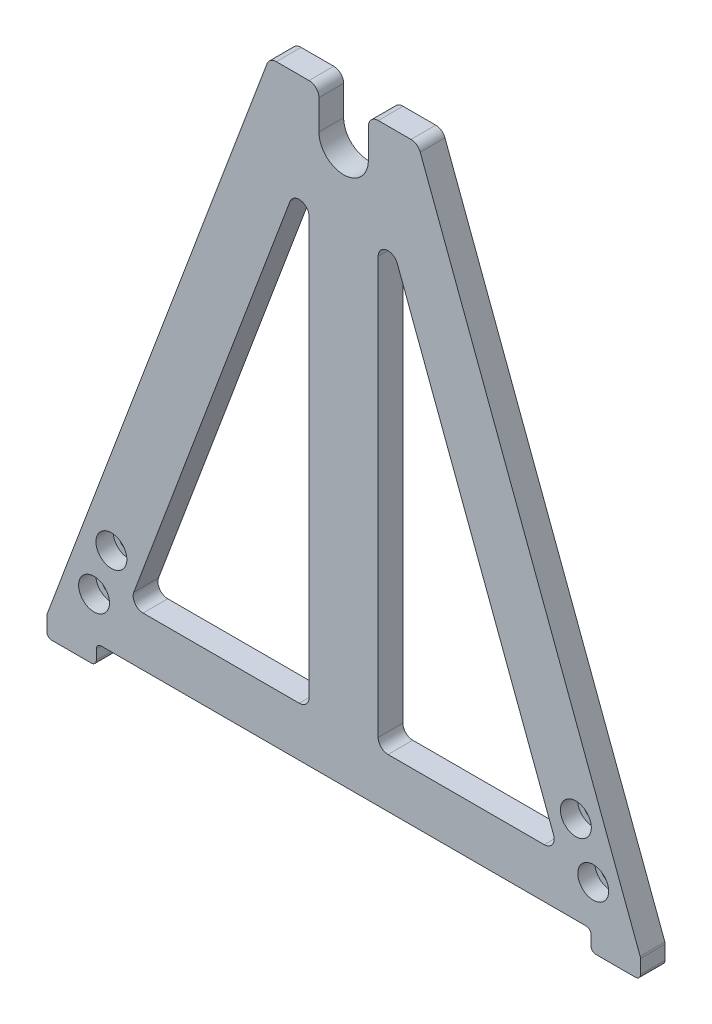
SolidWorks part; units mm, degrees
ref_plane "Front Plane" through (0, 0, 0) normal (0, 0, 1) x (1, 0, 0)
ref_plane "Top Plane" through (0, 0, 0) normal (0, 1, 0) x (1, 0, 0)
ref_plane "Right Plane" through (0, 0, 0) normal (1, 0, 0) x (0, 0, -1)
sketch "Sketch1" plane through (0, 0, 0) normal (0, 0, 1) x (1, 0, 0)
  line L0 (-19.6681, 150.7519) -> (-76.1191, 0.2156)
  line L1 (-62.23, 0) -> (62.23, 0)
  line L2 (76.1191, 0.2156) -> (19.6681, 150.7519)
  line L3 (0, 0) -> (0, 203.2) construction
  line L4 (0, -3.4925) -> (0, 3.4925) construction
  line L5 (3.4925, 0) -> (-3.4925, 0) construction
  line L6 (-76.2, 0) -> (76.2, 0) construction
  line L7 (17.2898, 152.4) -> (-17.2898, 152.4)
  line L8 (-76.2, -0.2303) -> (-76.2, -3.81)
  line L9 (-74.93, -5.08) -> (-64.77, -5.08)
  line L10 (-63.5, -1.27) -> (-63.5, -3.81)
  line L12 (76.2, -0.2303) -> (76.2, -3.81)
  line L13 (74.93, -5.08) -> (64.77, -5.08)
  line L14 (63.5, -1.27) -> (63.5, -3.81)
  arc A0 (76.2, -0.2303) -> (76.1191, 0.2156) centre (74.93, -0.2303) ccw
  arc A1 (-76.1191, 0.2156) -> (-76.2, -0.2303) centre (-74.93, -0.2303) ccw
  arc A2 (62.23, 0) -> (63.5, -1.27) centre (62.23, -1.27) cw
  arc A3 (-62.23, 0) -> (-63.5, -1.27) centre (-62.23, -1.27) ccw
  arc A4 (-76.2, -3.81) -> (-74.93, -5.08) centre (-74.93, -3.81) ccw
  arc A5 (-64.77, -5.08) -> (-63.5, -3.81) centre (-64.77, -3.81) ccw
  arc A6 (64.77, -5.08) -> (63.5, -3.81) centre (64.77, -3.81) cw
  arc A7 (76.2, -3.81) -> (74.93, -5.08) centre (74.93, -3.81) cw
  arc A8 (-17.2898, 152.4) -> (-19.6681, 150.7519) centre (-17.2898, 149.86) ccw
  arc A9 (17.2898, 152.4) -> (19.6681, 150.7519) centre (17.2898, 149.86) cw
  point P26 (-76.2, -5.08)
  point P29 (-63.5, -5.08)
  point P34 (76.2, -5.08)
  point P37 (-19.05, 152.4)
  point P42 (19.05, 152.4)
  dimension "D5" = 1.27
  dimension "D7" = 2.54
  dimension "D1" = 152.4
  dimension "D2" = 152.4
  dimension "D3" = 12.7
  dimension "D4" = 5.08
  dimension "D6" = 38.1
extrude "Boss-Extrude1" add sketch "Sketch1" along normal blind 6.35
sketch "Sketch2" plane through (0, 0, 0) normal (0, 0, -1) x (-1, 0, 0)
  line L0 (-8.8591, 15.24) -> (-8.8591, 122.1648)
  line L1 (-53.8742, 16.1319) -> (-13.7774, 123.0567)
  line L2 (-51.496, 12.7) -> (-11.3991, 12.7)
  line L3 (53.8742, 16.1319) -> (13.7774, 123.0567)
  line L4 (11.3991, 12.7) -> (51.496, 12.7)
  line L5 (8.8591, 15.24) -> (8.8591, 122.1648)
  line L6 (19.6681, 150.7519) -> (76.1191, 0.2156) construction
  line L8 (-8.8591, 12.7) -> (8.8591, 12.7) construction
  line L9 (0, 3.4925) -> (0, -3.4925) construction
  line L10 (-76.1191, 0.2156) -> (-19.6681, 150.7519) construction
  line L11 (62.23, 0) -> (-62.23, 0) construction
  arc A0 (-8.8591, 122.1648) -> (-13.7774, 123.0567) centre (-11.3991, 122.1648) ccw
  arc A1 (13.7774, 123.0567) -> (8.8591, 122.1648) centre (11.3991, 122.1648) ccw
  arc A2 (53.8742, 16.1319) -> (51.496, 12.7) centre (51.496, 15.24) cw
  arc A3 (11.3991, 12.7) -> (8.8591, 15.24) centre (11.3991, 15.24) cw
  arc A4 (-8.8591, 15.24) -> (-11.3991, 12.7) centre (-11.3991, 15.24) cw
  arc A5 (-53.8742, 16.1319) -> (-51.496, 12.7) centre (-51.496, 15.24) ccw
  point P6 (0, 12.7)
  dimension "D4" = 2.54
  dimension "D1" = 17.7183
  dimension "D2" = 15.24
  dimension "D3" = 12.7
extrude "Cut-Extrude1" cut sketch "Sketch2" against normal through all
sketch "Sketch3" plane through (0, 0, 0) normal (0, 0, -1) x (-1, 0, 0)
  line L1 (0, 142.24) -> (0, 152.4) construction
  line L2 (-17.2898, 152.4) -> (17.2898, 152.4) construction
  line L3 (-6.35, 142.24) -> (-6.35, 152.4)
  line L4 (-6.35, 152.4) -> (6.35, 152.4)
  line L5 (6.35, 152.4) -> (6.35, 142.24)
  arc A0 (-6.35, 142.24) -> (6.35, 142.24) centre (0, 142.24) ccw
  dimension "D1" = 12.7
  dimension "D2" = 10.16
extrude "Cut-Extrude2" cut sketch "Sketch3" against normal through all
fillet "Fillet1" radius 2.54 2 edges at (-6.35, 152.4, 3.175) (6.35, 152.4, 3.175)
ref_axis "Axis1" through (0, 142.24, 6.35) along (0, 0, -1)
hole_wizard "CBORE for #8 Socket Head Cap Screw1" positions "Sketch5" profile "Sketch4" counterbore size "#8" standard "ANSI Inch" end condition through all
sketch "Sketch5" plane through (0, 0, 6.35) normal (0, 0, 1) x (1, 0, 0)
  point P0 (-59.6198, 22.512)
  point P3 (-64.0791, 10.6206)
  point P6 (59.6198, 22.512)
  point P9 (64.0791, 10.6206)
sketch "Sketch4" plane through (-59.6198, 22.512, 6.35) normal (1, 0, 0) x (0, -1, 0)
  line L0 (0, 0) -> (0, 6.35)
  line L1 (0, 6.35) -> (2.4574, 6.35)
  line L3 (2.4574, 6.35) -> (2.4574, 4.4196)
  line L4 (2.4574, 4.4196) -> (3.9687, 4.4196)
  line L5 (3.9687, 4.4196) -> (3.9688, 0)
  line L7 (3.9688, 0) -> (0, 0)
  line L11 (0, -6.35) -> (0, 107.95) construction
  dimension "Thru Hole Dia." = 4.9149
  dimension "Thru Hole Depth" = 6.35
  dimension "C'Bore Dia." = 7.9375
  dimension "C'Bore Depth" = 4.4196
